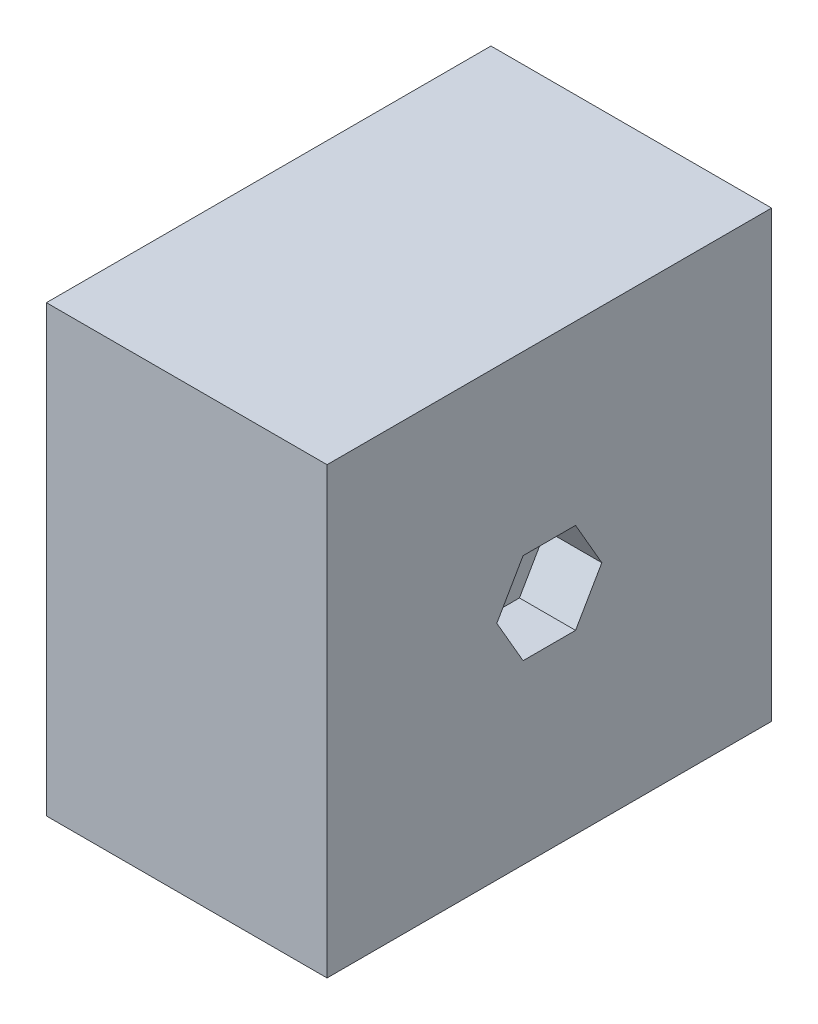
SolidWorks part; units mm, degrees
ref_plane "Płaszczyzna przednia" through (0, 0, 0) normal (0, 0, 1) x (1, 0, 0)
ref_plane "Płaszczyzna górna" through (0, 0, 0) normal (0, 1, 0) x (1, 0, 0)
ref_plane "Płaszczyzna prawa" through (0, 0, 0) normal (1, 0, 0) x (0, 0, -1)
sketch "Sketch1" plane through (0, 0, 0) normal (1, 0, 0) x (0, 0, -1)
  line L1 (-19.8, 19.8) -> (19.8, 19.8)
  line L2 (-19.8, 19.8) -> (-19.8, -19.8)
  line L3 (-19.8, -19.8) -> (19.8, -19.8)
  line L4 (19.8, 19.8) -> (19.8, -19.8)
  line L5 (-19.8, 19.8) -> (19.8, -19.8) construction
  line L6 (-19.8, -19.8) -> (19.8, 19.8) construction
  point P0 (0, 0)
  dimension "D1" = 39.6
  dimension "D2" = 39.6
extrude "Boss-Extrude1" add sketch "Sketch1" along normal blind 25
sketch "Sketch2" plane through (0, 0, 0) normal (1, 0, 0) x (0, 0, -1)
  line L2 (4.6765, 0) -> (2.3383, 4.05)
  line L3 (2.3383, 4.05) -> (-2.3383, 4.05)
  line L4 (-2.3383, 4.05) -> (-4.6765, 0)
  line L5 (-4.6765, 0) -> (-2.3383, -4.05)
  line L6 (-2.3383, -4.05) -> (2.3383, -4.05)
  line L7 (2.3383, -4.05) -> (4.6765, 0)
  circle A0 centre (0, 0) radius 4.05 construction
  dimension "D1" = 8.1
extrude "Cut-Extrude1" cut sketch "Sketch2" along normal blind 5
sketch "Sketch3" plane through (0, 0, 0) normal (1, 0, 0) x (0, 0, -1)
  circle A0 centre (0, 0) radius 2.75
  dimension "D1" = 5.5
extrude "Cut-Extrude2" cut sketch "Sketch3" against normal through all and the other way through all
extrude "Cut-Extrude4" cut sketch "Sketch2<2>" against normal blind 5 from surface starting at face at (25, 0, -2.75)
sketch "Sketch2<2>" plane through (0, 0, 0) normal (1, 0, 0) x (0, 0, -1) same geometry as "Sketch2"
